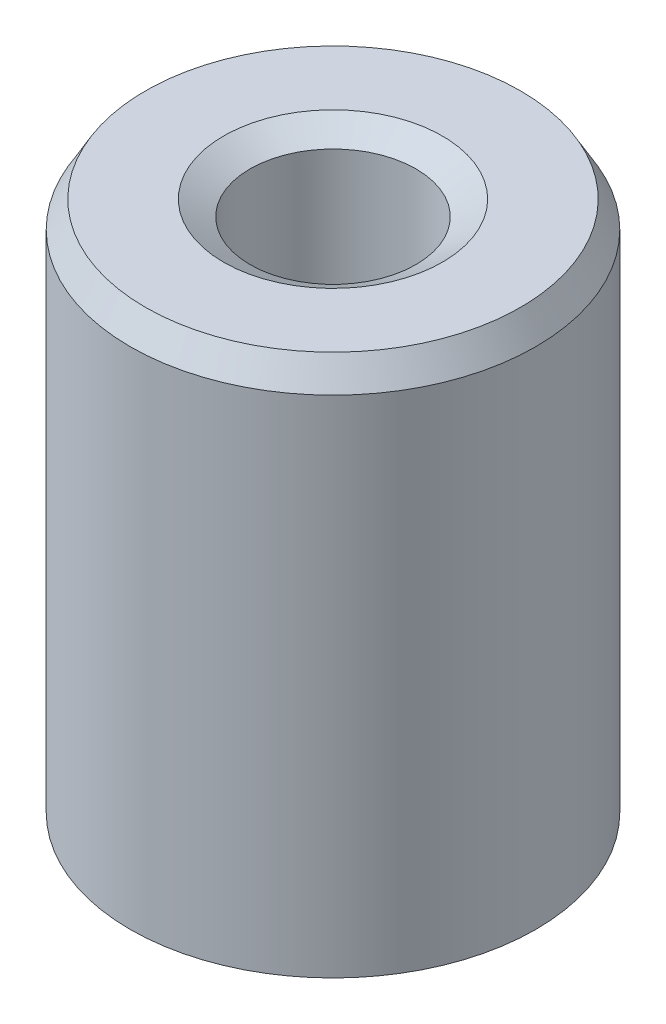
SolidWorks part; units mm, degrees
ref_plane "Front Plane" through (0, 0, 0) normal (0, 0, 1) x (1, 0, 0)
ref_plane "Top Plane" through (0, 0, 0) normal (0, 1, 0) x (1, 0, 0)
ref_plane "Right Plane" through (0, 0, 0) normal (1, 0, 0) x (0, 0, -1)
sketch "Sketch1" plane through (0, 0, 0) normal (0, 1, 0) x (1, 0, 0)
  circle A0 centre (0, 0) radius 20
  dimension "SLEEVE_OD" = 40
extrude "Boss-Extrude1" add sketch "Sketch1" along normal blind 53.8886
sketch "Sketch2" plane through (0, 0, 0) normal (0, 1, 0) x (1, 0, 0)
  circle A0 centre (0, 0) radius 8.1806
  dimension "BORE_D" = 16.3611
extrude "Cut-Extrude1" cut sketch "Sketch2" along normal through all
chamfer "Chamfer1" distance 2.6069 angle 30 4 edges at (0, 53.8886, 8.1806) (0, 0, 8.1806) (0, 0, 20) (0, 53.8886, 20) first distance on face at (0, 53.8886, 8.1806) first distance on face at (0, 0, 8.1806) first distance on face at (0, 53.8886, 20)
